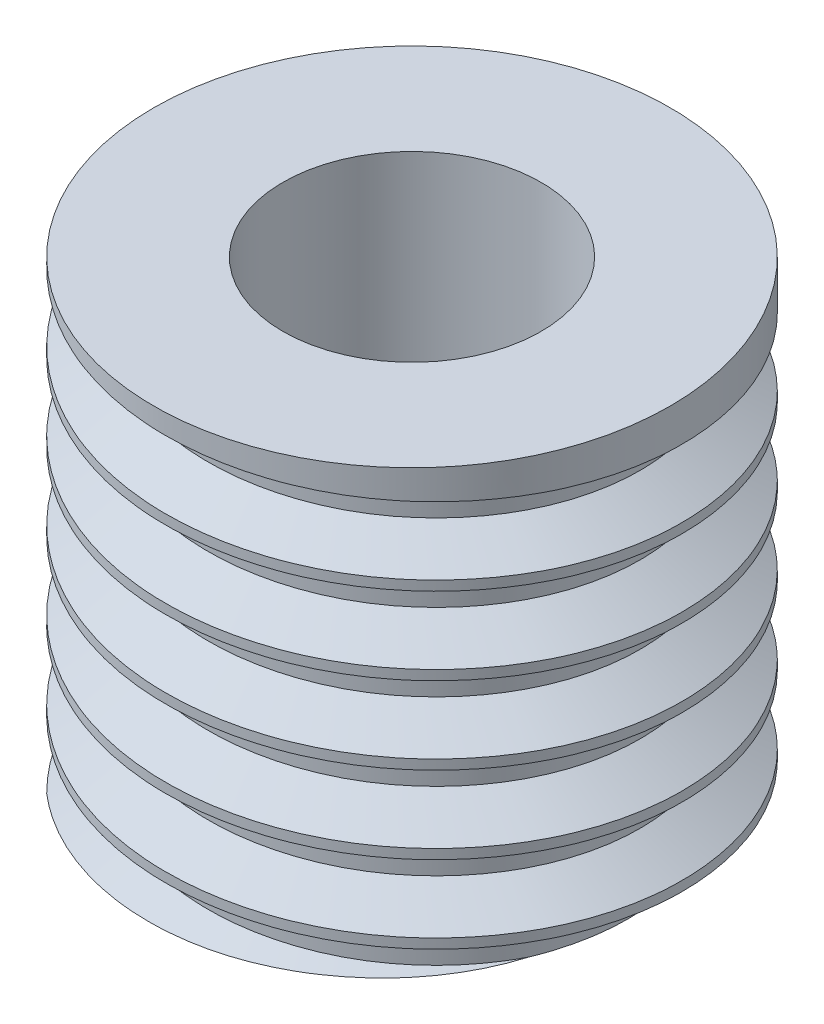
SolidWorks part; units mm, degrees
ref_plane "Front Plane" through (0, 0, 0) normal (0, 0, 1) x (1, 0, 0)
ref_plane "Top Plane" through (0, 0, 0) normal (0, 1, 0) x (1, 0, 0)
ref_plane "Right Plane" through (0, 0, 0) normal (1, 0, 0) x (0, 0, -1)
sketch "Sketch1" plane through (0, 0, 0) normal (0, 1, 0) x (1, 0, 0)
  circle A0 centre (0, 0) radius 2.5
  circle A1 centre (0, 0) radius 5
  dimension "D2" = 5
  dimension "D1" = 10
extrude "Boss-Extrude1" add sketch "Sketch1" along normal blind 9
thread "Thread1" start angle 0, offset 0, length 10, pitch 1.5, diameter 10
ref_plane "Plane1" through (-5, 9, 0) normal (0, 0, 1) x (-1, 0, 0)
sketch "Thread Profile1" plane through (-5, 9, 0) normal (0, 0, 1) x (-1, 0, 0)
  line L0 (0, 0) -> (0, 1.5) construction
  line L11 (0, 0) -> (0, 1.3125)
  line L12 (0, 1.3125) -> (-0.8119, 0.8437)
  line L13 (-0.8119, 0.8437) -> (-0.8119, 0.4687)
  line L15 (-0.8119, 0.4687) -> (0, 0)
  line L17 (-0.8119, 0.6562) -> (0, 0.6562) construction
  point P2 (0, 0)
  dimension "Pitch" = 1.5
  dimension "Profile_Angle" = 60
  dimension "Profile_Land" = 0.375
  dimension "Profile_Height" = 0.8119
